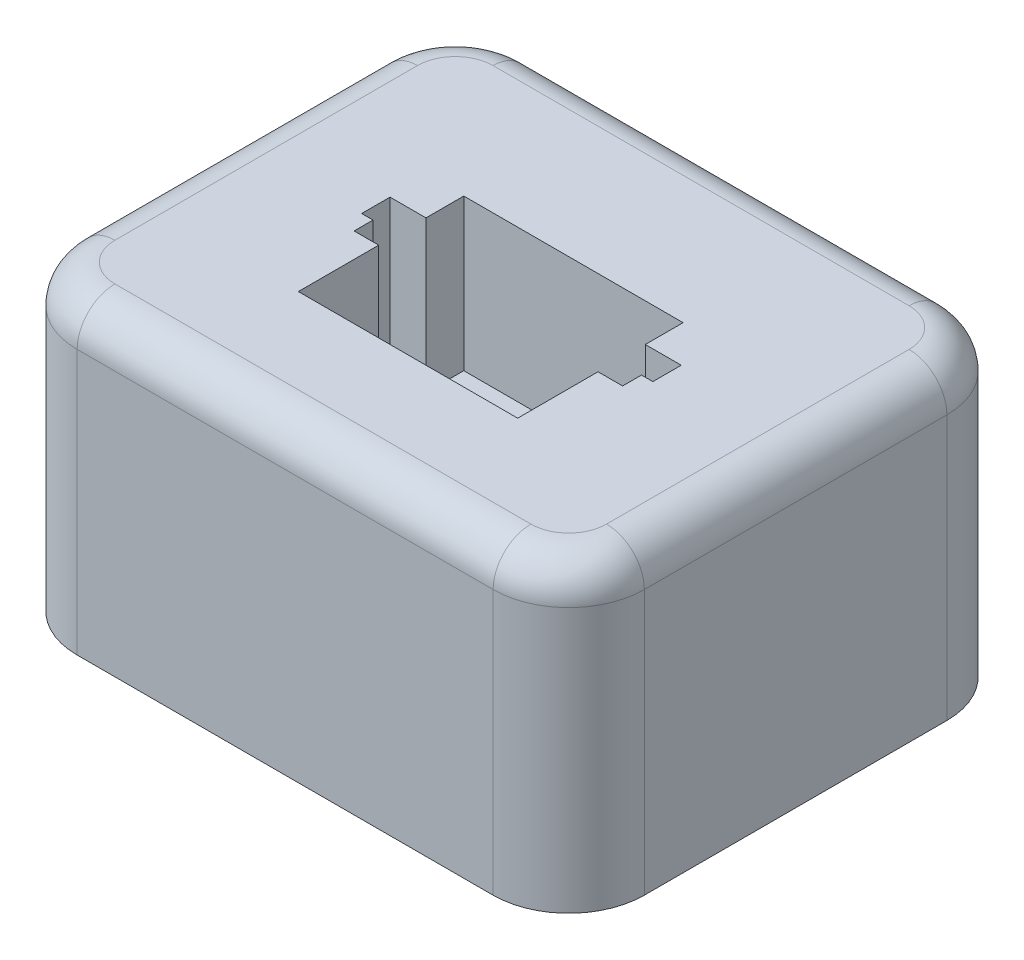
SolidWorks part; units mm, degrees
ref_plane "Спереди" through (0, 0, 0) normal (0, 0, 1) x (1, 0, 0)
ref_plane "Сверху" through (0, 0, 0) normal (0, 1, 0) x (1, 0, 0)
ref_plane "Справа" through (0, 0, 0) normal (1, 0, 0) x (0, 0, -1)
sketch "Эскиз1" plane through (0, 0, 0) normal (0, 1, 0) x (1, 0, 0)
  line L1 (4, 0) -> (26, 0)
  line L2 (0, 4) -> (0, 20)
  line L3 (4, 24) -> (26, 24)
  line L4 (30, 4) -> (30, 20)
  arc A0 (26, 24) -> (30, 20) centre (26, 20) cw
  arc A1 (26, 0) -> (30, 4) centre (26, 4) ccw
  arc A2 (4, 0) -> (0, 4) centre (4, 4) cw
  arc A3 (0, 20) -> (4, 24) centre (4, 20) cw
  point P10 (30, 0)
  point P13 (0, 0)
  point P16 (0, 24)
  dimension "D3" = 4
  dimension "D1" = 30
  dimension "D2" = 24
extrude "Тело" add sketch "Эскиз1" along normal blind 16
fillet "Скругление1" radius 2 8 edges at (15, 16, 0) (28.8284, 16, -1.1716) (1.1716, 16, -1.1716) (0, 16, -12) (1.1716, 16, -22.8284) (15, 16, -24) (28.8284, 16, -22.8284) (30, 16, -12)
sketch "Эскиз6" plane through (0, 0, 0) normal (0, -1, 0) x (1, 0, 0)
  circle A0 centre (4, -4) radius 1
  circle A1 centre (26, -4) radius 1
  circle A2 centre (26, -20) radius 1
  circle A3 centre (4, -20) radius 1
  dimension "D1" = 2
extrude "Крепеж" cut sketch "Эскиз6" against normal blind 7
sketch "Эскиз3" plane through (0, 16, 0) normal (0, 1, 0) x (1, 0, 0)
  line L1 (9.2, 9.5) -> (20.8, 9.5)
  line L2 (9.2, 9.5) -> (9.2, 6.5)
  line L3 (9.2, 6.5) -> (20.8, 6.5)
  line L4 (20.8, 9.5) -> (20.8, 6.5)
  line L5 (4, 0) -> (26, 0) construction
  point P7 (15, 0)
  point P11 (15, 6.5)
  dimension "D1" = 11.6
  dimension "D2" = 3
  dimension "D3" = 6.5
extrude "Разъем" cut sketch "Эскиз3" against normal up to next
sketch "Эскиз2" plane through (0, 16, 0) normal (0, 1, 0) x (1, 0, 0)
  line L1 (7.3, 13.25) -> (22.7, 13.25)
  line L2 (7.3, 13.25) -> (7.3, 11.75)
  line L3 (7.3, 11.75) -> (22.7, 11.75)
  line L4 (22.7, 13.25) -> (22.7, 11.75)
  line L5 (20.8, 9.5) -> (9.2, 9.5) construction
  line L6 (20.8, 6.5) -> (20.8, 9.5) construction
  point P4 (15, 11.75)
  point P9 (20.8, 8)
  point P10 (22.7, 12.5)
  point P11 (15, 9.5)
  dimension "D1" = 1.5
  dimension "D2" = 15.4
  dimension "D4" = 4.5
extrude "Плата" cut sketch "Эскиз2" against normal offset from surface (8 mm away) 8 up to face at (15, 0, -8)
sketch "Эскиз7" plane through (0, 16, 0) normal (0, 1, 0) x (1, 0, 0)
  line L0 (7.3, 11.75) -> (22.7, 11.75) construction
  line L1 (9.2, 9.5) -> (20.8, 9.5)
  line L2 (9.2, 9.5) -> (9.2, 11.75)
  line L3 (9.2, 11.75) -> (20.8, 11.75)
  line L4 (20.8, 9.5) -> (20.8, 11.75)
extrude "Вырез-Вытянуть2" cut sketch "Эскиз7" against normal up to surface (8 mm away) up to face at (15, 8, -12.5)
sketch "Эскиз8" plane through (0, 16, 0) normal (0, 1, 0) x (1, 0, 0)
  line L0 (7.3, 13.25) -> (7.3, 11.75) construction
  line L1 (7.9, 11.75) -> (22.1, 11.75)
  line L2 (7.9, 11.75) -> (7.9, 10.75)
  line L3 (7.9, 10.75) -> (22.1, 10.75)
  line L4 (22.1, 11.75) -> (22.1, 10.75)
  line L5 (22.7, 11.75) -> (22.7, 13.25) construction
  line L7 (7.3, 11.75) -> (9.2, 11.75) construction
  dimension "D1" = 0.6
  dimension "D2" = 0.6
  dimension "D3" = 1
extrude "Вырез-Вытянуть3" cut sketch "Эскиз8" against normal up to surface (8 mm away) up to face at (15, 8, -11.5625)
sketch "Эскиз9" plane through (0, 16, 0) normal (0, 1, 0) x (1, 0, 0)
  line L0 (22.7, 13.25) -> (7.3, 13.25) construction
  line L1 (9.2, 13.25) -> (20.8, 13.25)
  line L2 (9.2, 13.25) -> (9.2, 15.25)
  line L3 (9.2, 15.25) -> (20.8, 15.25)
  line L4 (20.8, 13.25) -> (20.8, 15.25)
  line L5 (9.2, 10.75) -> (9.2, 6.5) construction
  line L6 (20.8, 6.5) -> (20.8, 10.75) construction
  dimension "D1" = 2
extrude "Вырез-Вытянуть4" cut sketch "Эскиз9" against normal up to surface (8 mm away) up to face at (15, 8, -11.2917)
